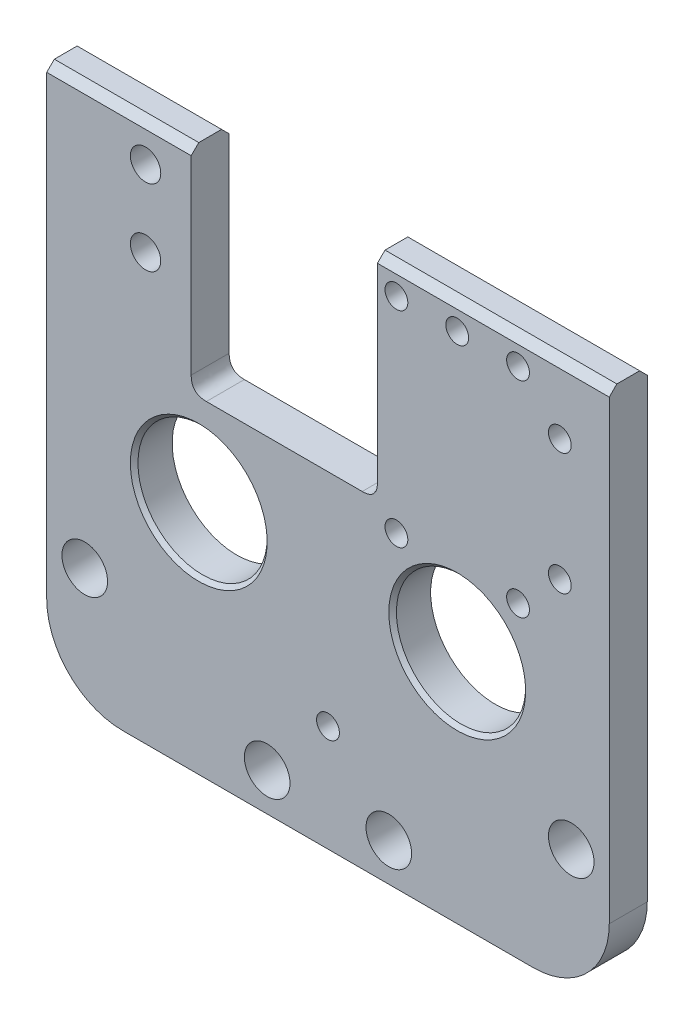
SolidWorks part; units mm, degrees
material "Stop 1060"
ref_plane "Płaszczyzna przednia" through (0, 0, 0) normal (0, 0, 1) x (1, 0, 0)
ref_plane "Płaszczyzna górna" through (0, 0, 0) normal (0, 1, 0) x (1, 0, 0)
ref_plane "Płaszczyzna prawa" through (0, 0, 0) normal (1, 0, 0) x (0, 0, -1)
sketch "Szkic1" plane through (0, 0, 0) normal (0, 0, 1) x (1, 0, 0)
  line L2 (34, 36) -> (34, -35)
  line L3 (34, -35) -> (-20, -35)
  line L6 (-20, -35) -> (-20, 36)
  line L7 (-20, 36) -> (34, 36)
  dimension "D1" = 71
  dimension "D2" = 20
  dimension "D3" = 54
  dimension "D4" = 36
extrude "Dodanie-wyciągnięcie1" add sketch "Szkic1" along normal blind 5
sketch "Szkic2" plane through (0, 0, 5) normal (0, 0, 1) x (1, 0, 0)
  line L1 (-20, 36) -> (3.5, 36)
  line L2 (-20, 36) -> (-20, 8)
  line L3 (-20, 8) -> (3.5, 8)
  line L4 (3.5, 36) -> (3.5, 8)
  dimension "D1" = 28
  dimension "D2" = 23.5
extrude "Wytnij-wyciągnięcie1" cut sketch "Szkic2" against normal blind 5
sketch "Szkic3" plane through (0, 0, 0) normal (0, 0, -1) x (-1, 0, 0)
  line L0 (-3.5, 8) -> (-3.5, 36) construction
  line L1 (-3.5, 30.5) -> (-24.5, 30.5)
  line L2 (-3.5, 30.5) -> (-3.5, 9.5)
  line L3 (-3.5, 9.5) -> (-24.5, 9.5)
  line L4 (-24.5, 30.5) -> (-24.5, 9.5)
  line L5 (-34, 36) -> (-3.5, 36) construction
  dimension "D1" = 5.5
  dimension "D2" = 21
  dimension "D3" = 21
extrude "Wytnij-wyciągnięcie2" cut sketch "Szkic3" against normal blind 3
sketch "Szkic4" plane through (0, 0, 5) normal (0, 0, 1) x (1, 0, 0)
  line L0 (3.5, 8) -> (3.5, 36) construction
  line L1 (34, 36) -> (3.5, 36) construction
  circle A0 centre (6, 32.5) radius 1.5
  circle A1 centre (14, 32.5) radius 1.5
  circle A2 centre (22, 32.5) radius 1.5
  circle A4 centre (22, 5.5) radius 1.5
  circle A5 centre (6, 5.5) radius 1.5
  circle A6 centre (27.5, 27) radius 1.5
  circle A7 centre (27.5, 11) radius 1.5
  circle A8 centre (14, 5.5) radius 1.5 [skipped]
  dimension "D1" = 2.5
  dimension "D2" = 3
  dimension "D4" = 3
  dimension "D6" = 8
  dimension "D8" = 5.5
  dimension "D10" = 3
  dimension "D3" = 3.5
  dimension "D5" = 2
  dimension "D7" = 27
  dimension "D9" = 5.5
  dimension "D11" = 2
extrude "Wytnij-wyciągnięcie3" cut sketch "Szkic4" against normal blind 5
sketch "Szkic5" plane through (0, 0, 5) normal (0, 0, 1) x (1, 0, 0)
  line L1 (-20, 8) -> (-40, 8)
  line L2 (-20, 8) -> (-20, -35)
  line L3 (-20, -35) -> (-40, -35)
  line L4 (-40, 8) -> (-40, -35)
  dimension "D1" = 20
  dimension "D2" = 43
extrude "Dodanie-wyciągnięcie2" add sketch "Szkic5" against normal blind 5
sketch "Szkic6" plane through (0, 0, 5) normal (0, 0, 1) x (1, 0, 0)
  line L0 (-40, 8) -> (-40, -35) construction
  line L1 (-40, 8) -> (3.5, 8) construction
  circle A0 centre (-20, -4) radius 8.5
  circle A1 centre (14, -4) radius 8.5
  dimension "D1" = 20
  dimension "D3" = 17
  dimension "D2" = 12
  dimension "D5" = 34
  dimension "D4" = 2
extrude "Wytnij-wyciągnięcie4" cut sketch "Szkic6" against normal blind 5
sketch "symetria" plane through (0, 0, 5) normal (0, 0, 1) x (1, 0, 0)
  line L0 (-20, -4) -> (14, -4)
  line L1 (-3, -4) -> (-3, -39)
  dimension "D1" = 35
sketch "Szkic7" plane through (0, 0, 5) normal (0, 0, 1) x (1, 0, 0)
  line L0 (-3, -4) -> (-3, -39) construction
  line L1 (-40, -35) -> (34, -35) construction
  line L2 (-3, -36.4153) -> (-3, -30)
  line L3 (-40, 8) -> (-40, -35) construction
  circle A0 centre (5, -30) radius 3
  circle A1 centre (-11, -30) radius 3
  circle A2 centre (-35, -19) radius 3
  circle A3 centre (29, -19) radius 3
  dimension "D1" = 6
  dimension "D4" = 6
  dimension "D2" = 8
  dimension "D3" = 5
  dimension "D5" = 5
  dimension "D6" = 16
extrude "Wytnij-wyciągnięcie5" cut sketch "Szkic7" against normal blind 10 contours A1 | A0 | A2 | A3 region at (5, -30, 5) region at (-11, -30, 5) region at (-35, -19, 5) region at (29, -19, 5)
fillet "Zaokrąglenie3" radius 10 2 edges at (34, -35, 2.5) (-40, -35, 2.5)
sketch "Szkic8" plane through (0, 0, 5) normal (0, 0, 1) x (1, 0, 0)
  line L1 (-40, 8) -> (-21, 8)
  line L2 (-40, 8) -> (-40, 36)
  line L3 (-40, 36) -> (-21, 36)
  line L4 (-21, 8) -> (-21, 36)
  dimension "D1" = 19
  dimension "D2" = 28
extrude "Dodanie-wyciągnięcie3" add sketch "Szkic8" against normal blind 5
fillet "Zaokrąglenie2" radius 2 2 edges at (3.5, 8, 2.5) (-21, 8, 2.5) conic rho 0.5
sketch "Szkic9" plane through (0, 0, 5) normal (0, 0, 1) x (1, 0, 0)
  line L2 (-21, 10) -> (-21, 36) construction
  line L3 (-21, 36) -> (-40, 36) construction
  circle A1 centre (-27, 31) radius 2
  circle A2 centre (-27, 21) radius 2
  dimension "D1" = 6
  dimension "D2" = 6
  dimension "D3" = 4
  dimension "D4" = 4
  dimension "D6" = 10
  dimension "D5" = 5
extrude "Wytnij-wyciągnięcie6" cut sketch "Szkic9" against normal blind 10
chamfer "Sfazowanie2" distance 1 angle 45 4 edges at (18.75, 36, 5) (18.75, 36, 0) (-30.5, 36, 0) (-30.5, 36, 5)
chamfer "Sfazowanie3" distance 0.5 angle 45 2 edges at (-11.5, -4, 5) (22.5, -4, 5)
sketch "Szkic10" plane through (0, 0, 5) normal (0, 0, 1) x (1, 0, 0)
  line L0 (-3, -4) -> (-3, -39) construction
  line L1 (-30, -35) -> (24, -35) construction
  circle A0 centre (-3, -21) radius 1.5
  dimension "D1" = 14
  dimension "D2" = 3
extrude "Wytnij-wyciągnięcie7" cut sketch "Szkic10" against normal blind 10
fillet "Zaokrąglenie4" radius 2 2 edges at (24.5, 9.5, 1.5) (24.5, 30.5, 1.5)
